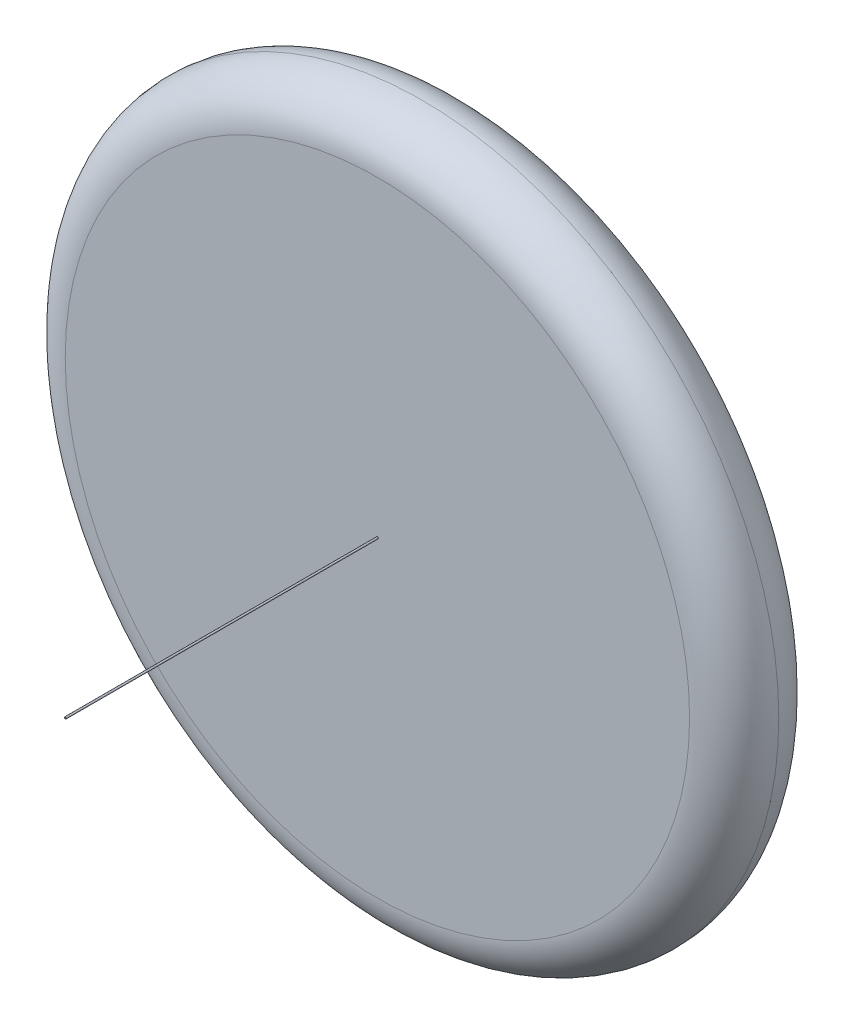
SolidWorks part; units mm, degrees
ref_plane "Front Plane" through (0, 0, 0) normal (0, 0, 1) x (1, 0, 0)
ref_plane "Top Plane" through (0, 0, 0) normal (0, 1, 0) x (1, 0, 0)
ref_plane "Right Plane" through (0, 0, 0) normal (1, 0, 0) x (0, 0, -1)
sketch "Sketch1" plane through (0, 0, 0) normal (0, 0, 1) x (1, 0, 0)
  circle A0 centre (0, 0) radius 8
extrude "Boss-Extrude1" add sketch "Sketch1" along normal blind 2
fillet "Fillet1" radius 1 2 edges at (8, 0, 0) (8, 0, 2)
sketch "Sketch3" plane through (0, 0, 2) normal (0, 0, 1) x (1, 0, 0)
  circle A0 centre (0, 0) radius 0.02
extrude "Boss-Extrude2" add sketch "Sketch3" along normal blind 7
